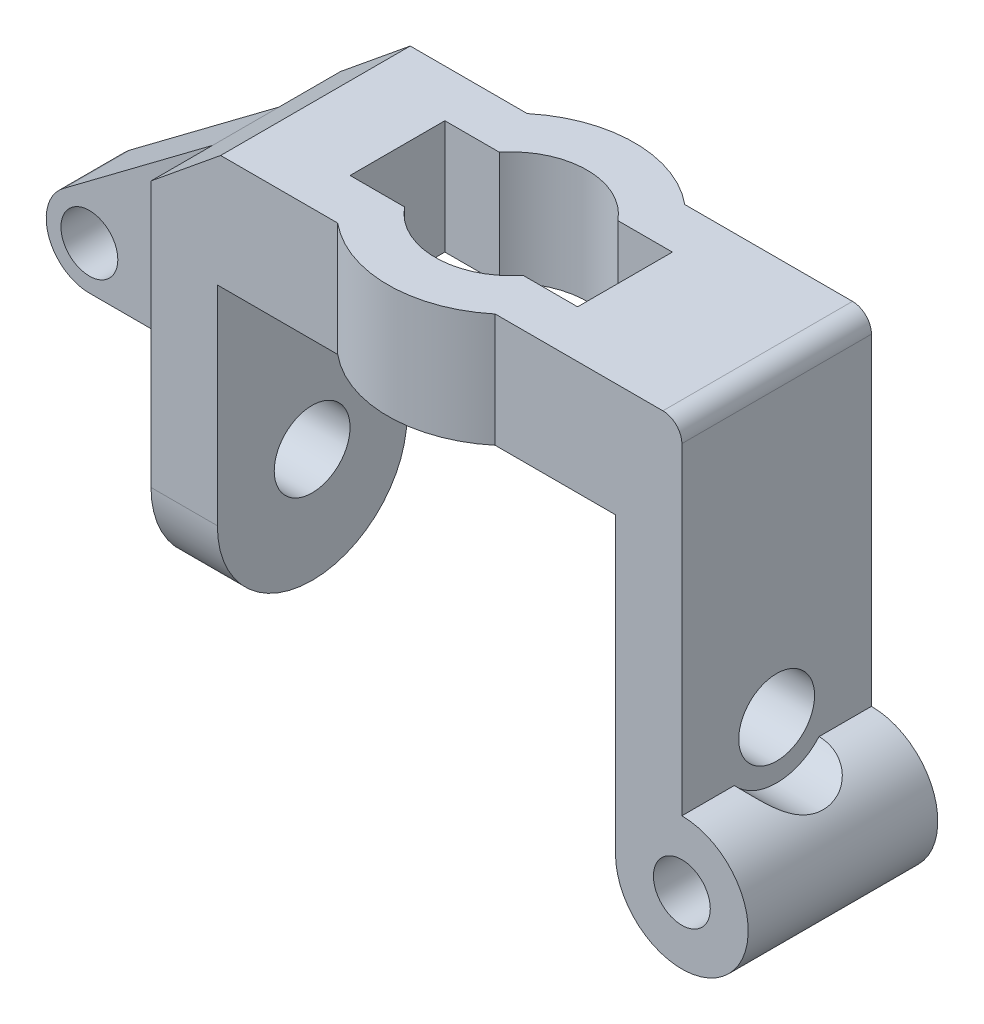
SolidWorks part; units mm, degrees
material "PBT General Purpose"
ref_plane "Front" through (0, 0, 0) normal (0, 0, 1) x (1, 0, 0)
ref_plane "Top" through (0, 0, 0) normal (0, 1, 0) x (1, 0, 0)
ref_plane "Right" through (0, 0, 0) normal (1, 0, 0) x (0, 0, -1)
sketch "Sketch1" plane through (0, 0, 0) normal (0, 0, 1) x (1, 0, 0)
  line L1 (0, 0) -> (3.5, 0)
  line L2 (0, 0) -> (0, 22)
  line L3 (0, 22) -> (3.5, 22)
  line L4 (3.5, 0) -> (3.5, 22)
  line L5 (0, 22) -> (28, 22)
  line L6 (0, 22) -> (0, 16)
  line L7 (0, 16) -> (28, 16)
  line L8 (28, 22) -> (28, 16)
  line L9 (28, 22) -> (24.5, 22)
  line L10 (28, 22) -> (28, -3)
  line L12 (24.5, 22) -> (24.5, 0.5)
  circle A0 centre (28, 0.5) radius 3.5
  point P11 (28, 0.5)
  dimension "D1" = 3.5
  dimension "D2" = 22
  dimension "D3" = 28
  dimension "D4" = 6
  dimension "D5" = 25
  dimension "D7" = 3.5
extrude "Boss-Extrude1" add sketch "Sketch1" along normal blind 10 contours L7 L2 L1 L4 | L12 L5 L4 L7 | L2 L7 L4 L3 | L5 L12 L7 L8 | A0 L10 L7 L12 | L10 A0 | L10 A0 region at (1.75, 8, 0) region at (1.75, 19, 0) region at (14, 19, 0) region at (26.25, 19, 0) region at (26.193, 9.6005, 0) region at (26.5146, 0.5, 0) region at (29.4854, 0.5, 0)
sketch "Sketch2" plane through (0, 22, 0) normal (0, 1, 0) x (1, 0, 0)
  line L0 (14, 0) -> (14, -50000) construction
  line L1 (0, 0) -> (28, 0) construction
  line L2 (0, -10) -> (28, -10) construction
  line L3 (0, -5) -> (28, -5) construction
  line L4 (0, -10) -> (0, 0) construction
  line L5 (28, -10) -> (28, 0) construction
  circle A0 centre (14, -5) radius 6.5
  point P4 (14, 0)
  point P7 (14, -10)
  dimension "D1" = 13
extrude "Boss-Extrude2" add sketch "Sketch2" against normal blind 6
sketch "Sketch4" plane through (0, 22, 0) normal (0, 1, 0) x (1, 0, 0)
  line L0 (0, -5) -> (28, -5) construction
  line L1 (0, -10) -> (0, 0) construction
  line L2 (28, -10) -> (28, 0) construction
  line L3 (28, -5) -> (14, 1.5) construction
  line L4 (14, 1.5) -> (14, -11.5) construction
  line L6 (8, -2.5) -> (20, -2.5)
  line L7 (8, -2.5) -> (8, -7.5)
  line L8 (8, -7.5) -> (20, -7.5)
  line L9 (20, -2.5) -> (20, -7.5)
  line L10 (8, -2.5) -> (20, -7.5) construction
  line L11 (8, -7.5) -> (20, -2.5) construction
  arc A0 (18.1533, 0) -> (9.8467, 0) centre (14, -5) ccw construction
  arc A1 (9.8467, -10) -> (18.1533, -10) centre (14, -5) ccw construction
  circle A2 centre (14, -5) radius 4
  dimension "D1" = 5
  dimension "D2" = 12
extrude "Cut-Extrude2" cut sketch "Sketch4" against normal blind 6 contours L8 A2 L6 | A2 L8 L9 L6 | A2 L6 L7 L8 | L6 A2 | L8 A2 region at (9.1536, 22, 5) region at (14, 22, 1.8892) region at (14, 22, 5) region at (18.8464, 22, 5) region at (14, 22, 8.1108)
sketch "Sketch5" plane through (0, 0, 10) normal (0, 0, 1) x (1, 0, 0)
  circle A0 centre (28, 0.5) radius 1.5
  dimension "D1" = 3
extrude "Cut-Extrude3" cut sketch "Sketch5" against normal through all
ref_plane "Plane1" through (0, 0, 5) normal (0, 0, 1) x (1, 0, 0)
sketch "Sketch6" plane through (0, 0, 5) normal (0, 0, 1) x (1, 0, 0)
  line L0 (4, 22) -> (0, 19)
  line L1 (3.5, 9) -> (-6.5, 9) construction
  line L2 (4, 22) -> (-7.8667, 13.1)
  line L3 (-6.5, 9) -> (3.5, 9)
  line L4 (3.5, 9) -> (-6.5, 9)
  line L5 (18.1533, 16) -> (24.5, 16)
  line L6 (18.1533, 22) -> (18.1533, 16)
  line L7 (28, 22) -> (18.1533, 22)
  line L8 (28, 4) -> (28, 22)
  line L9 (24.5, 16) -> (24.5, 0.5)
  line L10 (18.1533, 16) -> (24.5, 16)
  line L11 (18.1533, 22) -> (18.1533, 16)
  line L12 (28, 22) -> (18.1533, 22)
  line L13 (28, 4) -> (28, 22)
  line L14 (24.5, 16) -> (24.5, 0.5)
  line L16 (9.8467, 22) -> (0, 22)
  line L17 (9.8467, 16) -> (9.8467, 22)
  line L18 (3.5, 16) -> (9.8467, 16)
  line L19 (3.5, 0) -> (3.5, 16)
  line L20 (0, 0) -> (3.5, 0)
  line L21 (0, 22) -> (0, 0)
  line L22 (9.8467, 22) -> (0, 22)
  line L23 (9.8467, 16) -> (9.8467, 22)
  line L24 (3.5, 16) -> (9.8467, 16)
  line L25 (3.5, 0) -> (3.5, 16)
  line L26 (0, 0) -> (3.5, 0)
  line L27 (0, 22) -> (0, 0)
  line L33 (9.8467, 16) -> (9.8467, 22)
  line L34 (9.8467, 22) -> (0, 22)
  line L35 (0, 22) -> (0, 0)
  line L36 (0, 0) -> (3.5, 0)
  line L37 (3.5, 0) -> (3.5, 16)
  line L38 (3.5, 16) -> (9.8467, 16)
  line L39 (9.8467, 16) -> (9.8467, 22)
  line L40 (9.8467, 22) -> (0, 22)
  line L41 (0, 22) -> (0, 0)
  line L42 (0, 0) -> (3.5, 0)
  line L43 (3.5, 0) -> (3.5, 16)
  line L44 (3.5, 16) -> (9.8467, 16)
  circle A0 centre (-6.5, 11.2778) radius 2.2778
  arc A1 (24.5, 0.5) -> (28, 4) centre (28, 0.5) ccw
  arc A2 (24.5, 0.5) -> (28, 4) centre (28, 0.5) ccw
  point P13 (3.5, 9)
  point P18 (-8.5, 9)
  point P21 (-9.6, 11.8)
  dimension "D8" = 6.5
  dimension "D3" = 9
  dimension "D4" = 12
  dimension "D5" = 4
  dimension "D6" = 5
  dimension "D7" = 17
  dimension "D1" = 0
  dimension "D2" = 0
  dimension "D9" = 0
extrude "Boss-Extrude3" add sketch "Sketch6" along normal blind 1.75 and the other way blind 1.75 contours A0 L3 L27 L2 | A0 region at (-2.4076, 13.24, 5) region at (-6.5, 11.2778, 5)
sketch "Sketch10" plane through (0, 0, 5) normal (0, 0, 1) x (1, 0, 0)
  line L0 (0, 19) -> (-7.8667, 13.1) construction
  line L1 (-6.5, 9) -> (0, 9) construction
  line L2 (0, 9) -> (0, 19) construction
  line L3 (9.8467, 16) -> (9.8467, 22) construction
  line L4 (9.8467, 22) -> (0, 22) construction
  line L5 (0, 22) -> (0, 0) construction
  line L6 (0, 0) -> (3.5, 0) construction
  line L7 (3.5, 0) -> (3.5, 16) construction
  line L8 (3.5, 16) -> (9.8467, 16) construction
  line L9 (0, 19) -> (-7.8667, 13.1)
  line L10 (-6.5, 9) -> (0, 9)
  line L11 (0, 9) -> (0, 19)
  line L12 (9.8467, 16) -> (9.8467, 22)
  line L13 (9.8467, 22) -> (0, 22)
  line L14 (0, 22) -> (0, 0)
  line L15 (0, 0) -> (3.5, 0)
  line L16 (3.5, 0) -> (3.5, 16)
  line L17 (3.5, 16) -> (9.8467, 16)
  line L18 (2.7841, 21.274) -> (-38721.6548, -31608.1084) construction
  line L19 (3.673, 22) -> (0, 19)
  arc A0 (-7.8667, 13.1) -> (-6.5, 9) centre (-6.5, 11.2778) ccw construction
  arc A1 (-7.8667, 13.1) -> (-6.5, 9) centre (-6.5, 11.2778) ccw
extrude "Cut-Extrude6" cut sketch "Sketch10" against normal through all both and the other way through all contours L19 L13 L14 region at (1.2243, 21, 5)
fillet "Fillet1" radius 1 1 edges at (28, 22, 5)
fillet "Fillet2" radius 5 2 edges at (1.75, 0, 0) (1.75, 0, 10)
sketch "Sketch11" plane through (0, 0, 0) normal (1, 0, 0) x (0, 0, -1)
  line L12 (-5, 9) -> (-5, -5.2304) construction
  circle A0 centre (-5, 6) radius 2
extrude "Cut-Extrude7" cut sketch "Sketch11" along normal through all
ref_plane "Plane2" through (28, 0, 0) normal (1, 0, 0) x (0, 0, -1)
sketch "Sketch12" plane through (28, 0, 0) normal (1, 0, 0) x (0, 0, -1)
  circle A0 centre (-5, 6) radius 3
extrude "Cut-Extrude8" cut sketch "Sketch12" along normal through all
sketch "Sketch13" plane through (0, 0, 5) normal (0, 0, 1) x (1, 0, 0)
  circle A0 centre (-6.5, 11.2778) radius 1.5
extrude "Cut-Extrude9" cut sketch "Sketch13" against normal through all both and the other way through all
